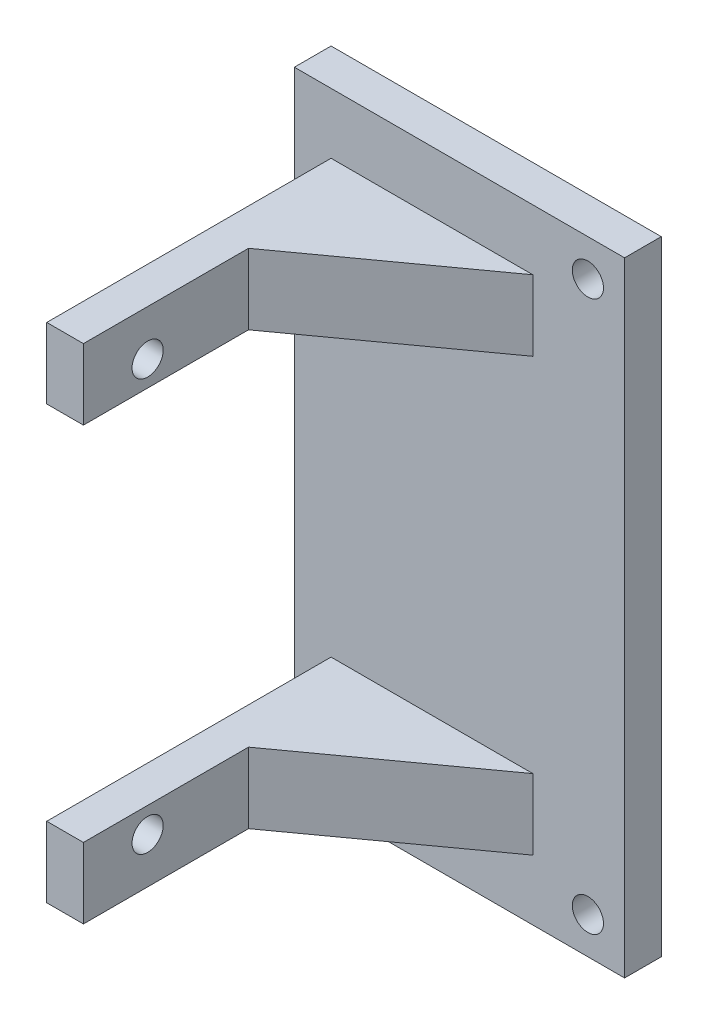
SolidWorks part; units mm, degrees
ref_plane "前视基准面" through (0, 0, 0) normal (0, 0, 1) x (1, 0, 0)
ref_plane "上视基准面" through (0, 0, 0) normal (0, 1, 0) x (1, 0, 0)
ref_plane "右视基准面" through (0, 0, 0) normal (1, 0, 0) x (0, 0, -1)
other "Configuration Table"
sketch "草图1" plane through (0, 0, 0) normal (0, 0, 1) x (1, 0, 0)
  line L1 (-84, -34) -> (-50, -34)
  line L2 (-84, -34) -> (-84, 34)
  line L3 (-84, 34) -> (-50, 34)
  line L4 (-50, -34) -> (-50, 34)
sketch "草图2" plane through (0, 0, 0) normal (0, 0, 1) x (1, 0, 0)
  line L1 (-80, -27.4) -> (-76, -27.4)
  line L2 (-80, -27.4) -> (-80, -19.7)
  line L3 (-80, -19.7) -> (-76, -19.7)
  line L4 (-76, -27.4) -> (-76, -19.7)
  line L5 (-80, 19.7) -> (-76, 19.7)
  line L6 (-80, 19.7) -> (-80, 27.4)
  line L7 (-80, 27.4) -> (-76, 27.4)
  line L8 (-76, 19.7) -> (-76, 27.4)
sketch "草图3" plane through (0, 0, 0) normal (0, 1, 0) x (1, 0, 0)
  line L0 (-76, -61) -> (-56, -61)
  line L1 (-56, -61) -> (-76, -87)
  line L2 (-76, -87) -> (-76, -61)
sketch "草图4" plane through (0, 0, 0) normal (0, 1, 0) x (1, 0, 0)
  line L0 (-76, -61) -> (-56, -61)
  line L1 (-56, -61) -> (-76, -87)
  line L2 (-76, -87) -> (-76, -61)
sketch "草图5" plane through (0, 0, 0) normal (0, 0, 1) x (1, 0, 0)
  circle A0 centre (-56, -30) radius 1.7
  circle A1 centre (-56, 30) radius 1.7
sketch "草图6" plane through (0, 0, 0) normal (1, 0, 0) x (0, 0, -1)
  circle A0 centre (-85, -22.44) radius 1.7
  circle A1 centre (-85, 22.44) radius 1.7
sketch "草图7" plane through (0, 0, 0) normal (0, 0, 1) x (1, 0, 0)
  line L1 (-84, -34) -> (-48, -34)
  line L2 (-84, -34) -> (-84, 34)
  line L3 (-84, 34) -> (-48, 34)
  line L4 (-48, -34) -> (-48, 34)
extrude "Base_4mm" add sketch "草图7" along normal blind 4 from offset 57
sketch "草图8" plane through (0, 0, 0) normal (0, 0, 1) x (1, 0, 0)
  line L1 (-80, -27.4) -> (-76, -27.4)
  line L2 (-80, -27.4) -> (-80, -19.7)
  line L3 (-80, -19.7) -> (-76, -19.7)
  line L4 (-76, -27.4) -> (-76, -19.7)
  line L6 (-80, 19.7) -> (-76, 19.7)
  line L7 (-80, 19.7) -> (-80, 27.4)
  line L8 (-80, 27.4) -> (-76, 27.4)
  line L9 (-76, 19.7) -> (-76, 27.4)
extrude "Twin_ear_supports" add sketch "草图8" along normal blind 31 from offset 61
sketch "草图9" plane through (0, 0, 0) normal (0, 1, 0) x (1, 0, 0)
  line L0 (-76, -61) -> (-58, -61)
  line L1 (-58, -61) -> (-76, -74)
  line L2 (-76, -74) -> (-76, -61)
extrude "Integral_short_gusset_-27.4" add sketch "草图9" along normal blind 7.7 from offset 27.4 offset against normal yes
sketch "草图10" plane through (0, 0, 0) normal (0, 1, 0) x (1, 0, 0)
  line L0 (-76, -61) -> (-58, -61)
  line L1 (-58, -61) -> (-76, -74)
  line L2 (-76, -74) -> (-76, -61)
extrude "Integral_short_gusset_19.7" add sketch "草图10" along normal blind 7.7 from offset 19.7
sketch "草图11" plane through (0, 0, 0) normal (0, 0, 1) x (1, 0, 0)
  circle A0 centre (-52, -30) radius 1.7
  circle A1 centre (-52, 30) radius 1.7
extrude "Base_M3_clearance" cut sketch "草图11" against normal blind 7 from offset 63
sketch "草图12" plane through (0, 0, 0) normal (1, 0, 0) x (0, 0, -1)
  circle A0 centre (-85, -22.44) radius 1.7
  circle A1 centre (-85, 22.44) radius 1.7
extrude "Actual_camera_44p88_pitch_M3" cut sketch "草图12" against normal blind 120 and the other way blind 120
